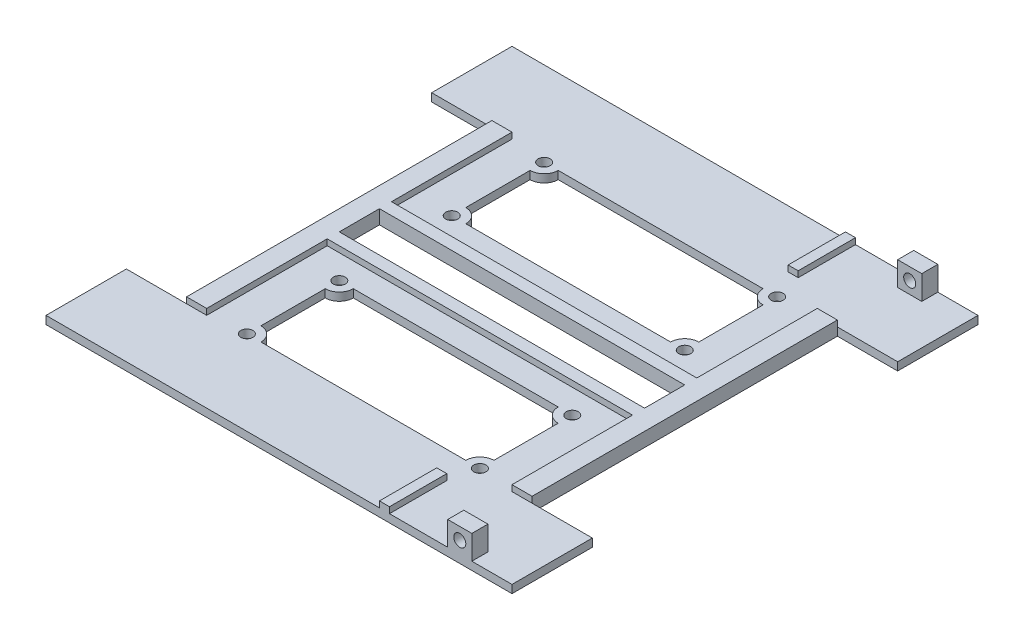
SolidWorks part; units mm, degrees
note: '?' marks a value the reader was unsure of.
ref_plane "Front Plane" through (0, 0, 0) normal (0, 0, 1) x (1, 0, 0)
ref_plane "Top Plane" through (0, 0, 0) normal (0, 1, 0) x (1, 0, 0)
ref_plane "Right Plane" through (0, 0, 0) normal (1, 0, 0) x (0, 0, -1)
sketch "Sketch1" plane through (0, 0, 0) normal (0, 1, 0) x (1, 0, 0)
  line L1 (58, 58) -> (-58, 58)
  line L2 (58, 58) -> (58, -58)
  line L3 (58, -58) -> (-58, -58)
  line L4 (-58, 58) -> (-58, -58)
  line L5 (58, 58) -> (-58, -58) construction
  line L6 (58, -58) -> (-58, 58) construction
  point P0 (0, 0)
  dimension "D1" = 116
  dimension "D2" = 116
extrude "Boss-Extrude1" add sketch "Sketch1" along normal blind 2
sketch "Sketch2" plane through (0, 2, 0) normal (0, 1, 0) x (1, 0, 0)
  line L0 (-58, 58) -> (-58, -58) construction
  line L1 (-58, 38) -> (-43, 38)
  line L2 (-58, 38) -> (-58, -38)
  line L3 (-58, -38) -> (-43, -38)
  line L4 (-43, 38) -> (-43, -38)
  line L5 (58, 58) -> (-58, 58) construction
  line L6 (-58, -58) -> (58, -58) construction
  dimension "D1" = 20
  dimension "D2" = 20
  dimension "D3" = 15
extrude "Cut-Extrude1" cut sketch "Sketch2" against normal up to next
ref_axis "Axis1" through (0, 1.05, 0) along (0, -1, 0)?
pattern_circular "CirPattern1" count 2 over 360 about axis through (0, 0, 0) along (0, 1, 0) of "Cut-Extrude1"
sketch "Sketch3" plane through (0, 2, 0) normal (0, 1, 0) x (1, 0, 0)
  circle A0 centre (-29, 37) radius 1.5
extrude "Cut-Extrude2" cut sketch "Sketch3" against normal up to next
sketch "Sketch4" plane through (0, 2, 0) normal (0, 1, 0) x (1, 0, 0)
  circle A0 centre (29, 37) radius 1.5
extrude "Cut-Extrude3" cut sketch "Sketch4" against normal up to next
pattern_linear "LPattern1" count 2 spacing 23 along (0, 0, 1) of "Cut-Extrude2", "Cut-Extrude3"
pattern_circular "CirPattern2" count 2 over 360 about axis through (0, 0, 0) along (0, 1, 0) of "LPattern1", "Cut-Extrude2", "Cut-Extrude3"
sketch "Sketch5" plane through (0, 2, 0) normal (0, 1, 0) x (1, 0, 0)
  line L1 (-38, -8) -> (38, -8)
  line L2 (-38, -8) -> (-38, 8)
  line L3 (-38, 8) -> (38, 8)
  line L4 (38, -8) -> (38, 8)
  line L5 (-38, -8) -> (38, 8) construction
  line L6 (-38, 8) -> (38, -8) construction
  point P0 (0, 0)
extrude "Cut-Extrude4" cut sketch "Sketch5" against normal up to next
sketch "Sketch6" plane through (0, 2, 0) normal (0, 1, 0) x (1, 0, 0)
  line L0 (-58, -58) -> (58, -58) construction
  line L1 (42, -58) -> (48, -58)
  line L2 (42, -58) -> (42, -54)
  line L3 (42, -54) -> (48, -54)
  line L4 (48, -58) -> (48, -54)
  line L6 (58, -58) -> (58, -38) construction
  dimension "D1" = 6
  dimension "D2" = 4
  dimension "D3" = 10
extrude "Boss-Extrude2" add sketch "Sketch6" along normal blind 6
sketch "Sketch7" plane through (0, 0, 58) normal (0, 0, 1) x (1, 0, 0)
  line L0 (42, 8) -> (48, 8) construction
  line L1 (48, 8) -> (48, 2) construction
  circle A0 centre (45, 5) radius 1.5
  dimension "D1" = 3
  dimension "D2" = 3
extrude "Cut-Extrude5" cut sketch "Sketch7" against normal up to next
mirror "Mirror1" about plane through (0, 0, 0) normal (0, 0, 1) of "Boss-Extrude2", "Cut-Extrude5"
sketch "Sketch8" plane through (0, 2, 0) normal (0, 1, 0) x (1, 0, 0)
  line L1 (-29, -37) -> (29, -37)
  line L2 (-29, -37) -> (-29, -14)
  line L3 (-29, -14) -> (29, -14)
  line L4 (29, -37) -> (29, -14)
  circle A0 centre (29, -37) radius 3.5
  circle A1 centre (29, -14) radius 3.5
  circle A2 centre (-29, -14) radius 3.5
  circle A3 centre (-29, -37) radius 3.5
  point P7 (-25.5, -37)
  point P8 (-29, -33.5)
  point P10 (-29, -17.5535)
  point P12 (-25.5, -14)
  point P14 (25.5, -37)
  point P15 (29, -33.5)
  point P16 (29, -17.5535)
  point P17 (25.5, -14)
extrude "Cut-Extrude7" cut sketch "Sketch8" against normal up to next contours A3 L1 A0 L4 A1 L3 A2 L2
mirror "Mirror2" about plane through (0, 0, 0) normal (0, 0, 1) of "Cut-Extrude7"
sketch "Sketch9" plane through (0, 2, 0) normal (0, 1, 0) x (1, 0, 0)
  line L1 (-43, 38) -> (-38, 38)
  line L2 (-43, 38) -> (-43, -38)
  line L3 (-43, -38) -> (-38, -38)
  line L4 (-38, 38) -> (-38, -38)
extrude "Boss-Extrude3" add sketch "Sketch9" along normal blind 1.5
mirror "Mirror3" about plane through (0, 0, 0) normal (1, 0, 0) of "Boss-Extrude3"
sketch "Sketch10" plane through (0, 0, 0) normal (0, -1, 0) x (-1, 0, 0)
  line L0 (-38, -8) -> (-38, 8) construction
  line L1 (38, 8) -> (-38, 8)
  line L2 (38, 8) -> (38, 5)
  line L3 (38, 5) -> (-38, 5)
  line L4 (-38, 8) -> (-38, 5)
  dimension "D1" = 3
extrude "Boss-Extrude4" add sketch "Sketch10" against normal blind 3.5
mirror "Mirror4" about plane through (0, 0, 0) normal (0, 0, 1) of "Boss-Extrude4"
sketch "Sketch11" plane through (0, 2, 0) normal (0, 1, 0) x (1, 0, 0)
  line L0 (-58, -58) -> (42, -58) construction
  line L1 (27.5, -58) -> (25, -58)
  line L2 (27.5, -58) -> (27.5, -43.7353)
  line L3 (27.5, -43.7353) -> (25, -43.7353)
  line L4 (25, -58) -> (25, -43.7353)
  line L6 (58, -58) -> (58, -38) construction
  dimension "D1" = 33
  dimension "D2" = 2.5
extrude "Boss-Extrude5" add sketch "Sketch11" along normal blind 1.5
mirror "Mirror5" about plane through (0, 0, 0) normal (0, 0, 1) of "Boss-Extrude5"
